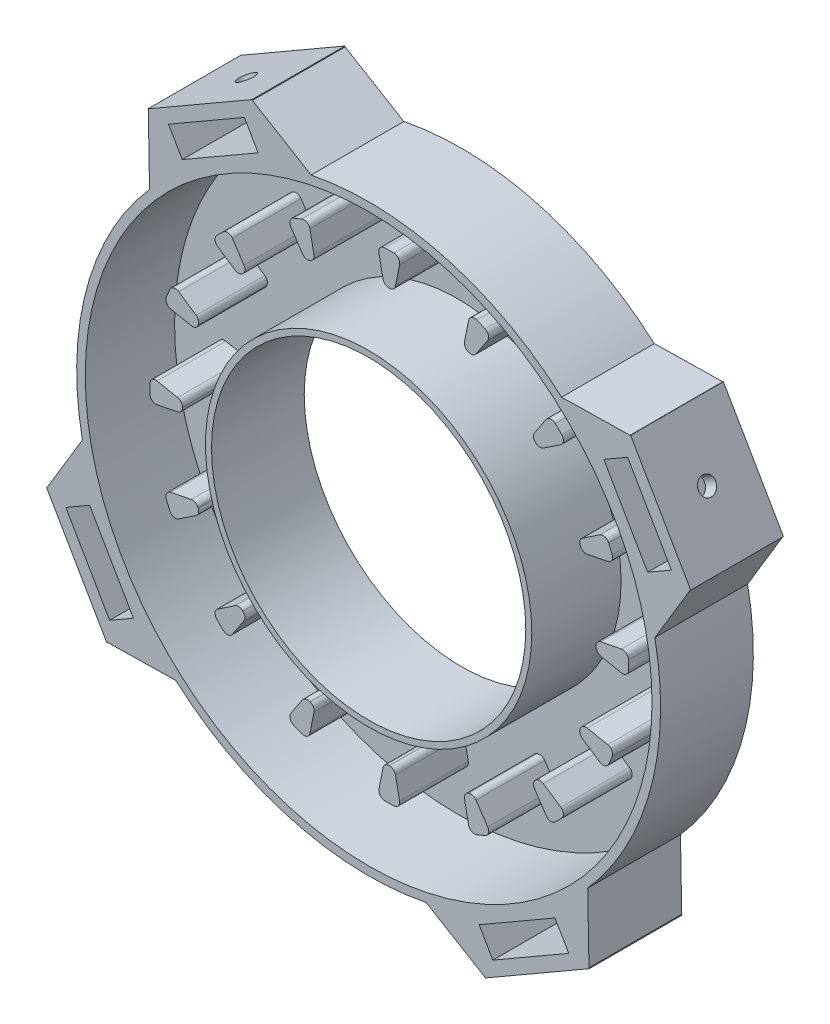
SolidWorks part; units mm, degrees
ref_plane "Front Plane" through (0, 0, 0) normal (0, 0, 1) x (1, 0, 0)
ref_plane "Top Plane" through (0, 0, 0) normal (0, 1, 0) x (1, 0, 0)
ref_plane "Right Plane" through (0, 0, 0) normal (1, 0, 0) x (0, 0, -1)
sketch "Sketch1" plane through (0, 0, 0) normal (0, 0, 1) x (1, 0, 0)
  line L0 (49.0393, -272.0695) -> (49.0393, -252.5605) construction
  line L1 (9.7545, -213.2757) -> (-9.7545, -213.2757) construction
  circle A0 centre (0, -262.315) radius 82.5
  circle A1 centre (0, -262.315) radius 47.5
  point P4 (49.0393, -262.315)
  point P7 (0, -213.2757)
  dimension "D1" = 165
  dimension "D2" = 95
extrude "Boss-Extrude1" add sketch "Sketch1" against normal blind 1
sketch "Sketch3" plane through (0, 0, 0) normal (0, 0, 1) x (1, 0, 0)
  circle A0 centre (0, -262.315) radius 47.5
  circle A1 centre (0, -262.315) radius 47.5 construction
  circle A2 centre (0, -262.315) radius 82.5
  circle A3 centre (0, -262.315) radius 45.75
  circle A4 centre (0, -262.315) radius 85
  circle M1 centre (0, -262.315) radius 47.5
  circle M2 centre (0, -262.315) radius 82.5
  dimension "D1" = 91.5
  dimension "D2" = 165
  dimension "D3" = 170
extrude "Boss-Extrude2" add sketch "Sketch3" along normal blind 26 and the other way up to surface (1 mm away) contours A4 M2 | A3 M1 region at (-46.1565, -262.315, 0) region at (-82.5958, -262.315, 0) other way up to face at (47.5, -262.315, -1)
sketch "Sketch4" plane through (0, 0, 0) normal (0, 0, 1) x (1, 0, 0)
  line L0 (0, -177.315) -> (0, -262.315) construction
  line L1 (0, -262.315) -> (-83.0192, -310.2462) construction
  line L2 (0, -262.315) -> (83.0192, -310.2462) construction
  line L3 (-93.7755, -296.2491) -> (-76.2755, -326.56)
  line L4 (-76.2755, -326.56) -> (-63.2851, -319.06)
  line L5 (-93.7755, -296.2491) -> (-80.7851, -288.7491)
  line L12 (-33.9341, -168.5395) -> (-26.4341, -181.5299)
  line L13 (-64.245, -186.0395) -> (-56.745, -199.0299)
  line L14 (-33.9341, -168.5395) -> (-64.245, -186.0395)
  line L15 (93.7755, -228.3809) -> (80.7851, -235.8809)
  line L16 (76.2755, -198.0701) -> (63.2851, -205.5701)
  line L17 (93.7755, -228.3809) -> (76.2755, -198.0701)
  line L18 (33.9341, -356.0905) -> (26.4341, -343.1002)
  line L19 (64.245, -338.5905) -> (56.745, -325.6002)
  line L20 (33.9341, -356.0905) -> (64.245, -338.5905)
  line L21 (-88.1529, -298.4877) -> (-75.4029, -320.5713)
  line L22 (-88.1529, -298.4877) -> (-81.2247, -294.4877)
  line L23 (-75.4029, -320.5713) -> (-68.4747, -316.5713)
  line L24 (-81.2247, -294.4877) -> (-68.4747, -316.5713)
  line L25 (-36.1727, -174.1621) -> (-58.2563, -186.9121)
  line L26 (-36.1727, -174.1621) -> (-32.1727, -181.0903)
  line L27 (-32.1727, -181.0903) -> (-54.2563, -193.8403)
  line L28 (-58.2563, -186.9121) -> (-54.2563, -193.8403)
  line L29 (88.1529, -226.1423) -> (75.4029, -204.0587)
  line L30 (88.1529, -226.1423) -> (81.2247, -230.1423)
  line L31 (81.2247, -230.1423) -> (68.4747, -208.0587)
  line L32 (75.4029, -204.0587) -> (68.4747, -208.0587)
  line L33 (36.1727, -350.4679) -> (58.2563, -337.7179)
  line L34 (36.1727, -350.4679) -> (32.1727, -343.5397)
  line L35 (32.1727, -343.5397) -> (54.2563, -330.7897)
  line L36 (58.2563, -337.7179) -> (54.2563, -330.7897)
  circle A0 centre (0, -262.315) radius 85 construction
  arc A1 (-63.2851, -319.06) -> (-80.7851, -288.7491) centre (0, -262.315) cw
  arc A4 (-56.745, -199.0299) -> (-26.4341, -181.5299) centre (0, -262.315) cw
  arc A5 (63.2851, -205.5701) -> (80.7851, -235.8809) centre (0, -262.315) cw
  arc A6 (56.745, -325.6002) -> (26.4341, -343.1002) centre (0, -262.315) cw
  point P11 (-81.7779, -309.5295)
  point P22 (0, -262.315)
  point P28 (0, -262.315)
  point P46 (0, -262.315)
  dimension "D2" = 35
  dimension "D1" = 120
  dimension "D3" = 15
  dimension "D5" = 25.5
  dimension "D6" = 3.75
  dimension "D7" = 8
  dimension "D4" = 4
  dimension "D8" = 4
extrude "Boss-Extrude3" add sketch "Sketch4" along normal up to surface and the other way up to surface up to face at (82.5, -262.315, 26) other way up to face at (85, -262.315, -1)
sketch "Sketch8" plane through (0, 0, 0) normal (0, 0, 1) x (1, 0, 0)
  line L0 (0, -151.636) -> (0, -262.315) construction
  line L2 (95.8508, -317.6545) -> (0, -262.315) construction
  line L4 (-85.0255, -311.4045) -> (0, -262.315) construction
  line L5 (-93.7755, -296.2491) -> (-76.2755, -326.56) construction
  line L6 (3.2501, -194.7552) -> (2.059, -200.7431) construction
  line L7 (-2.059, -200.7431) -> (-3.2501, -194.7552) construction
  line L8 (3.0049, -194.7064) -> (1.8138, -200.6943)
  line L9 (-1.8138, -200.6943) -> (-3.0049, -194.7064)
  line L10 (28.6488, -201.0027) -> (25.257, -206.079)
  line L11 (21.9055, -204.6908) -> (23.0965, -198.7029)
  line L12 (49.9313, -216.6333) -> (44.855, -220.0252)
  line L13 (42.2899, -217.46) -> (45.6817, -212.3837)
  line L14 (63.6121, -239.2185) -> (57.6242, -240.4095)
  line L15 (56.236, -237.058) -> (61.3123, -233.6662)
  line L16 (67.6086, -265.3199) -> (61.6207, -264.1288)
  line L17 (61.6207, -260.5012) -> (67.6086, -259.3101)
  line L18 (61.3123, -290.9639) -> (56.236, -287.572)
  line L19 (57.6242, -284.2205) -> (63.6121, -285.4115)
  line L20 (45.6817, -312.2463) -> (42.2899, -307.17)
  line L21 (44.855, -304.6049) -> (49.9313, -307.9967)
  line L22 (23.0965, -325.9271) -> (21.9055, -319.9393)
  line L23 (25.257, -318.551) -> (28.6488, -323.6273)
  line L24 (-3.0049, -329.9236) -> (-1.8138, -323.9357)
  line L25 (1.8138, -323.9357) -> (3.0049, -329.9236)
  line L26 (-28.6488, -323.6273) -> (-25.257, -318.551)
  line L27 (-21.9055, -319.9393) -> (-23.0965, -325.9271)
  line L28 (-49.9313, -307.9967) -> (-44.855, -304.6049)
  line L29 (-42.2899, -307.17) -> (-45.6817, -312.2463)
  line L30 (-63.6121, -285.4115) -> (-57.6242, -284.2205)
  line L31 (-56.236, -287.572) -> (-61.3123, -290.9639)
  line L32 (-67.6086, -259.3101) -> (-61.6207, -260.5012)
  line L33 (-61.6207, -264.1288) -> (-67.6086, -265.3199)
  line L34 (-61.3123, -233.6662) -> (-56.236, -237.058)
  line L35 (-57.6242, -240.4095) -> (-63.6121, -239.2185)
  line L36 (-45.6817, -212.3837) -> (-42.2899, -217.46)
  line L37 (-44.855, -220.0252) -> (-49.9313, -216.6333)
  line L38 (-23.0965, -198.7029) -> (-21.9055, -204.6908)
  line L39 (-25.257, -206.079) -> (-28.6488, -201.0027)
  line L40 (-1.2885, -194.365) -> (1.2885, -194.365) construction
  line L41 (0, -197.565) -> (-10.7081, -197.565) construction
  line L42 (-80.7851, -288.7491) -> (-93.7755, -296.2491) construction
  line L43 (-76.2755, -326.56) -> (-63.2851, -319.06) construction
  circle A0 centre (0, -262.315) radius 64.75 construction
  arc A1 (-1.3264, -192.3654) -> (-3.2501, -194.7552) centre (-1.2885, -194.365) ccw construction
  arc A2 (1.3264, -192.3654) -> (-1.3264, -192.3654) centre (0, -262.3528) ccw construction
  arc A3 (3.2501, -194.7552) -> (1.3264, -192.3654) centre (1.2885, -194.365) ccw construction
  arc A4 (0.0943, -202.3529) -> (2.059, -200.7431) centre (0.0975, -200.3529) ccw construction
  arc A5 (0.0943, -202.3529) -> (-0.0943, -202.3529) centre (0, -262.3528) ccw construction
  arc A6 (-2.059, -200.7431) -> (-0.0943, -202.3529) centre (-0.0975, -200.3529) ccw construction
  arc A7 (0.0947, -202.1029) -> (1.8138, -200.6943) centre (0.0975, -200.3529) ccw
  arc A8 (0.0947, -202.1029) -> (-0.0947, -202.1029) centre (0, -262.3528) ccw
  arc A9 (-1.8138, -200.6943) -> (-0.0947, -202.1029) centre (-0.0975, -200.3529) ccw
  arc A10 (-1.3217, -192.6153) -> (-3.0049, -194.7064) centre (-1.2885, -194.365) ccw
  arc A11 (1.3217, -192.6153) -> (-1.3217, -192.6153) centre (0, -262.3528) ccw
  arc A12 (3.0049, -194.7064) -> (1.3217, -192.6153) centre (1.2885, -194.365) ccw
  arc A13 (23.1297, -206.7225) -> (25.257, -206.079) centre (23.8019, -205.1068) ccw
  arc A14 (23.1297, -206.7225) -> (22.9547, -206.65) centre (-0.0145, -262.3499) ccw
  arc A15 (21.9055, -204.6908) -> (22.9547, -206.65) centre (23.6218, -205.0322) ccw
  arc A16 (25.4518, -197.4151) -> (23.0965, -198.7029) centre (24.8129, -199.0443) ccw
  arc A17 (27.894, -198.4267) -> (25.4518, -197.4151) centre (-0.0145, -262.3499) ccw
  arc A18 (28.6488, -201.0027) -> (27.894, -198.4267) centre (27.1938, -200.0305) ccw
  arc A19 (42.6434, -219.8056) -> (44.855, -220.0252) centre (43.8828, -218.5701) ccw
  arc A20 (42.6434, -219.8056) -> (42.5094, -219.6716) centre (-0.0267, -262.3417) ccw
  arc A21 (42.2899, -217.46) -> (42.5094, -219.6716) centre (43.7449, -218.4323) ccw
  arc A22 (48.3506, -212.0953) -> (45.6817, -212.3837) centre (47.1368, -213.356) ccw
  arc A23 (50.2197, -213.9645) -> (48.3506, -212.0953) centre (-0.0267, -262.3417) ccw
  arc A24 (49.9313, -216.6333) -> (50.2197, -213.9645) centre (48.959, -215.1782) ccw
  arc A25 (55.665, -239.3603) -> (57.6242, -240.4095) centre (57.2828, -238.6932) ccw
  arc A26 (55.665, -239.3603) -> (55.5925, -239.1853) centre (-0.0349, -262.3295) ccw
  arc A27 (56.236, -237.058) -> (55.5925, -239.1853) centre (57.2083, -238.5131) ccw
  arc A28 (63.8883, -234.421) -> (61.3123, -233.6662) centre (62.2845, -235.1212) ccw
  arc A29 (64.8999, -236.8632) -> (63.8883, -234.421) centre (-0.0349, -262.3295) ccw
  arc A30 (63.6121, -239.2185) -> (64.8999, -236.8632) centre (63.2707, -237.5021) ccw
  arc A31 (60.2121, -262.4097) -> (61.6207, -264.1288) centre (61.9621, -262.4125) ccw
  arc A32 (60.2121, -262.4097) -> (60.2121, -262.2203) centre (-0.0378, -262.315) ccw
  arc A33 (61.6207, -260.5012) -> (60.2121, -262.2203) centre (61.9621, -262.2176) ccw
  arc A34 (69.6997, -260.9933) -> (67.6086, -259.3101) centre (67.95, -261.0265) ccw
  arc A35 (69.6997, -263.6367) -> (69.6997, -260.9933) centre (-0.0378, -262.315) ccw
  arc A36 (67.6086, -265.3199) -> (69.6997, -263.6367) centre (67.95, -263.6035) ccw
  arc A37 (55.5925, -285.4447) -> (56.236, -287.572) centre (57.2083, -286.1169) ccw
  arc A38 (55.5925, -285.4447) -> (55.665, -285.2697) centre (-0.0349, -262.3005) ccw
  arc A39 (57.6242, -284.2205) -> (55.665, -285.2697) centre (57.2828, -285.9369) ccw
  arc A40 (64.8999, -287.7669) -> (63.6121, -285.4115) centre (63.2707, -287.1279) ccw
  arc A41 (63.8883, -290.209) -> (64.8999, -287.7669) centre (-0.0349, -262.3005) ccw
  arc A42 (61.3123, -290.9639) -> (63.8883, -290.209) centre (62.2845, -289.5088) ccw
  arc A43 (42.5094, -304.9584) -> (42.2899, -307.17) centre (43.7449, -306.1978) ccw
  arc A44 (42.5094, -304.9584) -> (42.6434, -304.8245) centre (-0.0267, -262.2883) ccw
  arc A45 (44.855, -304.6049) -> (42.6434, -304.8245) centre (43.8828, -306.0599) ccw
  arc A46 (50.2197, -310.6656) -> (49.9313, -307.9967) centre (48.959, -309.4518) ccw
  arc A47 (48.3506, -312.5347) -> (50.2197, -310.6656) centre (-0.0267, -262.2883) ccw
  arc A48 (45.6817, -312.2463) -> (48.3506, -312.5347) centre (47.1368, -311.274) ccw
  arc A49 (22.9547, -317.98) -> (21.9055, -319.9393) centre (23.6218, -319.5979) ccw
  arc A50 (22.9547, -317.98) -> (23.1297, -317.9075) centre (-0.0145, -262.2801) ccw
  arc A51 (25.257, -318.551) -> (23.1297, -317.9075) centre (23.8019, -319.5233) ccw
  arc A52 (27.894, -326.2033) -> (28.6488, -323.6273) centre (27.1938, -324.5995) ccw
  arc A53 (25.4518, -327.2149) -> (27.894, -326.2033) centre (-0.0145, -262.2801) ccw
  arc A54 (23.0965, -325.9271) -> (25.4518, -327.2149) centre (24.8129, -325.5857) ccw
  arc A55 (-0.0947, -322.5271) -> (-1.8138, -323.9357) centre (-0.0975, -324.2771) ccw
  arc A56 (-0.0947, -322.5271) -> (0.0947, -322.5271) centre (0, -262.2772) ccw
  arc A57 (1.8138, -323.9357) -> (0.0947, -322.5271) centre (0.0975, -324.2771) ccw
  arc A58 (1.3217, -332.0147) -> (3.0049, -329.9236) centre (1.2885, -330.265) ccw
  arc A59 (-1.3217, -332.0147) -> (1.3217, -332.0147) centre (0, -262.2772) ccw
  arc A60 (-3.0049, -329.9236) -> (-1.3217, -332.0147) centre (-1.2885, -330.265) ccw
  arc A61 (-23.1297, -317.9075) -> (-25.257, -318.551) centre (-23.8019, -319.5233) ccw
  arc A62 (-23.1297, -317.9075) -> (-22.9547, -317.98) centre (0.0145, -262.2801) ccw
  arc A63 (-21.9055, -319.9393) -> (-22.9547, -317.98) centre (-23.6218, -319.5979) ccw
  arc A64 (-25.4518, -327.2149) -> (-23.0965, -325.9271) centre (-24.8129, -325.5857) ccw
  arc A65 (-27.894, -326.2033) -> (-25.4518, -327.2149) centre (0.0145, -262.2801) ccw
  arc A66 (-28.6488, -323.6273) -> (-27.894, -326.2033) centre (-27.1938, -324.5995) ccw
  arc A67 (-42.6434, -304.8245) -> (-44.855, -304.6049) centre (-43.8828, -306.0599) ccw
  arc A68 (-42.6434, -304.8245) -> (-42.5094, -304.9584) centre (0.0267, -262.2883) ccw
  arc A69 (-42.2899, -307.17) -> (-42.5094, -304.9584) centre (-43.7449, -306.1978) ccw
  arc A70 (-48.3506, -312.5347) -> (-45.6817, -312.2463) centre (-47.1368, -311.274) ccw
  arc A71 (-50.2197, -310.6656) -> (-48.3506, -312.5347) centre (0.0267, -262.2883) ccw
  arc A72 (-49.9313, -307.9967) -> (-50.2197, -310.6656) centre (-48.959, -309.4518) ccw
  arc A73 (-55.665, -285.2697) -> (-57.6242, -284.2205) centre (-57.2828, -285.9369) ccw
  arc A74 (-55.665, -285.2697) -> (-55.5925, -285.4447) centre (0.0349, -262.3005) ccw
  arc A75 (-56.236, -287.572) -> (-55.5925, -285.4447) centre (-57.2083, -286.1169) ccw
  arc A76 (-63.8883, -290.209) -> (-61.3123, -290.9639) centre (-62.2845, -289.5088) ccw
  arc A77 (-64.8999, -287.7669) -> (-63.8883, -290.209) centre (0.0349, -262.3005) ccw
  arc A78 (-63.6121, -285.4115) -> (-64.8999, -287.7669) centre (-63.2707, -287.1279) ccw
  arc A79 (-60.2121, -262.2203) -> (-61.6207, -260.5012) centre (-61.9621, -262.2176) ccw
  arc A80 (-60.2121, -262.2203) -> (-60.2121, -262.4097) centre (0.0378, -262.315) ccw
  arc A81 (-61.6207, -264.1288) -> (-60.2121, -262.4097) centre (-61.9621, -262.4125) ccw
  arc A82 (-69.6997, -263.6367) -> (-67.6086, -265.3199) centre (-67.95, -263.6035) ccw
  arc A83 (-69.6997, -260.9933) -> (-69.6997, -263.6367) centre (0.0378, -262.315) ccw
  arc A84 (-67.6086, -259.3101) -> (-69.6997, -260.9933) centre (-67.95, -261.0265) ccw
  arc A85 (-55.5925, -239.1853) -> (-56.236, -237.058) centre (-57.2083, -238.5131) ccw
  arc A86 (-55.5925, -239.1853) -> (-55.665, -239.3603) centre (0.0349, -262.3295) ccw
  arc A87 (-57.6242, -240.4095) -> (-55.665, -239.3603) centre (-57.2828, -238.6932) ccw
  arc A88 (-64.8999, -236.8632) -> (-63.6121, -239.2185) centre (-63.2707, -237.5021) ccw
  arc A89 (-63.8883, -234.421) -> (-64.8999, -236.8632) centre (0.0349, -262.3295) ccw
  arc A90 (-61.3123, -233.6662) -> (-63.8883, -234.421) centre (-62.2845, -235.1212) ccw
  arc A91 (-42.5094, -219.6716) -> (-42.2899, -217.46) centre (-43.7449, -218.4323) ccw
  arc A92 (-42.5094, -219.6716) -> (-42.6434, -219.8056) centre (0.0267, -262.3417) ccw
  arc A93 (-44.855, -220.0252) -> (-42.6434, -219.8056) centre (-43.8828, -218.5701) ccw
  arc A94 (-50.2197, -213.9645) -> (-49.9313, -216.6333) centre (-48.959, -215.1782) ccw
  arc A95 (-48.3506, -212.0953) -> (-50.2197, -213.9645) centre (0.0267, -262.3417) ccw
  arc A96 (-45.6817, -212.3837) -> (-48.3506, -212.0953) centre (-47.1368, -213.356) ccw
  arc A97 (-22.9547, -206.65) -> (-21.9055, -204.6908) centre (-23.6218, -205.0322) ccw
  arc A98 (-22.9547, -206.65) -> (-23.1297, -206.7225) centre (0.0145, -262.3499) ccw
  arc A99 (-25.257, -206.079) -> (-23.1297, -206.7225) centre (-23.8019, -205.1068) ccw
  arc A100 (-27.894, -198.4267) -> (-28.6488, -201.0027) centre (-27.1938, -200.0305) ccw
  arc A101 (-25.4518, -197.4151) -> (-27.894, -198.4267) centre (0.0145, -262.3499) ccw
  arc A102 (-23.0965, -198.7029) -> (-25.4518, -197.4151) centre (-24.8129, -199.0443) ccw
  point P253 (0, -262.315)
  dimension "D1" = 120
  dimension "D7" = 129.5
  dimension "D9" = 11.25
  dimension "D2" = 2.577
  dimension "D3" = 0.1949
  dimension "D4" = 5.9879
  dimension "D8" = 3.2
  dimension "D5" = 0.25
  dimension "D6" = 16
extrude "Boss-Extrude4" add sketch "Sketch8" along normal blind 20
sketch "Sketch9" plane through (64.4962, -111.7107, 0) normal (-0.5, 0.866, 0) x (0.866, 0.5, 0)
  line L0 (-113.6575, -26) -> (-148.6575, -26) construction
  line L1 (-113.6575, -26) -> (-113.6575, 1) construction
  circle A0 centre (-131.1575, -12.5) radius 2.5
  point P5 (-131.1575, -26)
  point P8 (-113.6575, -12.5)
  dimension "D1" = 5
extrude "Cut-Extrude1" cut sketch "Sketch9" against normal blind 5
pattern_circular "CirPattern1" count 4 over 360 about axis through (0, -262.315, -241.4163) along (0, 0, 1) of "Cut-Extrude1"
chamfer "Chamfer2" distance 12 angle 45 4 edges at (-56.745, -199.0299, 12.5) (63.2851, -205.5701, 12.5) (56.745, -325.6002, 12.5) (-63.2851, -319.06, 12.5) first distance on face at (-75.4344, -242.1024, 12.5) first distance on face at (20.2126, -186.8806, 12.5) first distance on face at (75.4344, -282.5276, 12.5) first distance on face at (-20.2126, -337.7494, 12.5)
chamfer "Chamfer3" distance 12 angle 45 4 edges at (-80.7851, -288.7491, 12.5) (26.4341, -343.1002, 12.5) (80.7851, -235.8809, 12.5) (-26.4341, -181.5299, 12.5) first distance on face at (-77.7716, -246.3146, 12.5) first distance on face at (-16.0004, -340.0867, 12.5) first distance on face at (77.7716, -278.3154, 12.5) first distance on face at (16.0004, -184.5434, 12.5)
